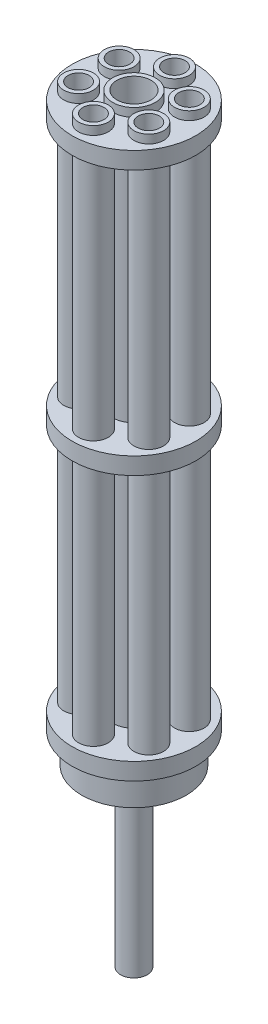
SolidWorks part; units mm, degrees
other "Markup1"
sketch "Sketch5" plane through (-15, 6, 15) normal (0, 1, 0) x (-1, 0, 0)
ref_plane "Front Plane" through (0, 0, 0) normal (0, 0, 1) x (1, 0, 0)
ref_plane "Top Plane" through (0, 0, 0) normal (0, 1, 0) x (1, 0, 0)
ref_plane "Right Plane" through (0, 0, 0) normal (1, 0, 0) x (0, 0, -1)
sketch "Sketch1" plane through (0, 0, 0) normal (0, 1, 0) x (1, 0, 0)
  circle A15 centre (0, 0) radius 14.5
  dimension "D1" = 29
extrude "Boss-Extrude1" add sketch "Sketch1" along normal blind 4
sketch "Sketch2" plane through (0, 4, 0) normal (0, 1, 0) x (1, 0, 0)
  line L0 (0, 0) -> (0, 9.5) construction
  line L1 (0, 0) -> (-8.2272, 4.75) construction
  line L2 (0, 0) -> (-8.2272, -4.75) construction
  line L3 (0, 9.5) -> (-8.2272, 4.75) construction
  line L4 (0, 0) -> (-2.4588, 9.1763) construction
  line L6 (0, 0) -> (-7.25, 12.5574) construction
  circle A0 centre (0, 0) radius 5
  circle A1 centre (0, 9.5) radius 3.48
  circle A2 centre (8.2272, 4.75) radius 3.48
  circle A3 centre (8.2272, -4.75) radius 3.48
  circle A4 centre (0, -9.5) radius 3.48
  circle A5 centre (-8.2272, -4.75) radius 3.48
  circle A6 centre (-8.2272, 4.75) radius 3.48
  circle A7 centre (0, 0) radius 4
  circle A8 centre (-8.2272, 4.75) radius 2.48
  circle A9 centre (0, 9.5) radius 2.48
  circle A10 centre (8.2272, 4.75) radius 2.48
  circle A11 centre (8.2272, -4.75) radius 2.48
  circle A12 centre (0, -9.5) radius 2.48
  circle A13 centre (-8.2272, -4.75) radius 2.48
  circle A14 centre (0, 0) radius 9.5 construction
  circle A15 centre (0, 0) radius 14.5 construction
  arc A16 (-6.7175, 6.7175) -> (-2.4588, 9.1763) centre (0, 0) cw construction
  arc A17 (6.7175, 6.7175) -> (9.1763, 2.4588) centre (0, 0) cw construction
  arc A18 (6.7175, 6.7175) -> (9.1763, 2.4588) centre (0, 0) cw construction
  point P17 (0, 0)
  point P31 (-6.0795, 5.99)
  point P32 (-2.1477, 8.26)
  point P33 (-2.4588, 9.1763)
  point P34 (-6.7175, 6.7175)
  dimension "D1" = 10
  dimension "D2" = 15
  dimension "D7" = 1
  dimension "D3" = 9.5
  dimension "D5" = 30
  dimension "D6" = 6
extrude "Boss-Extrude2" add sketch "Sketch2" along normal blind 2 and the other way blind 125
pattern_linear "LPattern4" count 3 spacing 62 along (0, -1, 0) of "Boss-Extrude1"
sketch "Sketch3" plane through (0, 4, 0) normal (0, 1, 0) x (1, 0, 0)
  circle A0 centre (0, 9.5) radius 2.48 construction
  circle A1 centre (0, 0) radius 4
  circle A2 centre (0, 0) radius 4
  circle A3 centre (-8.2272, 4.75) radius 2.48 construction
  circle A4 centre (-8.2272, -4.75) radius 2.48 construction
  circle A5 centre (0, -9.5) radius 2.48 construction
  circle A6 centre (8.2272, -4.75) radius 2.48 construction
  circle A7 centre (8.2272, 4.75) radius 2.48 construction
  circle A8 centre (0, 9.5) radius 2.48
  circle A9 centre (-8.2272, 4.75) radius 2.48
  circle A10 centre (-8.2272, -4.75) radius 2.48
  circle A11 centre (0, -9.5) radius 2.48
  circle A12 centre (8.2272, -4.75) radius 2.48
  circle A13 centre (8.2272, 4.75) radius 2.48
  dimension "D1" = 0
extrude "Cut-Extrude1" [suppressed] cut sketch "Sketch3" against normal through all
sketch "Sketch4" plane through (0, -124, 0) normal (0, -1, 0) x (1, 0, 0)
  circle A0 centre (0, 0) radius 5.2
  dimension "D1" = 10.4
extrude "Cut-Extrude2" [suppressed] cut sketch "Sketch4" against normal offset from surface (58 mm away) 4 up to face at (-8.2272, 4, -1.27)
sketch "Sketch6" plane through (0, -124, 0) normal (0, -1, 0) x (1, 0, 0)
  line L0 (-16.7447, 7) -> (-12.6984, 7) construction
  line L1 (-16.7447, 7) -> (-16.7447, 3) construction
  line L2 (-16.7447, 3) -> (-16.7447, 0) construction
  line L3 (-16.7447, 0) -> (-19.7447, 0) construction
  line L4 (-19.7447, 0) -> (0, 0) construction
  line L5 (0, 0) -> (0, 14.5) construction
  arc A0 (-13.874, 4.2145) -> (-16.7447, 3) centre (-16.7447, 7) cw
  arc A2 (-16.7447, 3) -> (-16.7447, -3) centre (-16.7447, 0) ccw
  arc A3 (-13.874, -4.2145) -> (-16.7447, -3) centre (-16.7447, -7) ccw
  arc A4 (-13.874, 4.2145) -> (-13.874, -4.2145) centre (0, 0) ccw
  circle A5 centre (-16.7447, 0) radius 1.75
  circle A6 centre (0, 0) radius 14.5 construction
  point P21 (-19.7447, 0)
  dimension "D1" = 90
  dimension "D3" = 3
  dimension "D4" = 4
  dimension "D6" = 3.5
  dimension "D2" = 90
  dimension "D5" = 8.4291
extrude "Boss-Extrude3" [suppressed] add sketch "Sketch6" against normal up to surface (4 mm away)
mirror "Mirror1" [suppressed] about plane through (0, 0, 0) normal (1, 0, 0)
sketch "Sketch7" plane through (0, 0, 0) normal (1, 0, 0) x (0, 0, -1)
  line L0 (-1.27, 6) -> (-8.23, 6) construction
  line L1 (-14.5, 6) -> (14.5, 6)
  line L2 (-14.5, 6) -> (-14.5, -124)
  line L3 (-14.5, -124) -> (14.5, -124)
  line L4 (14.5, 6) -> (14.5, -124)
  line L6 (-14.5, -124) -> (14.5, -124) construction
  point P11 (0, 6)
  dimension "D1" = 29
extrude "Short Cut" [suppressed] cut sketch "Sketch7" against normal through all and the other way through all
sketch "Sketch8" plane through (0, 4, 0) normal (0, 1, 0) x (1, 0, 0)
  circle A0 centre (-8.2272, -4.75) radius 2.48 construction
  circle A1 centre (0, -9.5) radius 2.48 construction
  circle A2 centre (8.2272, -4.75) radius 2.48 construction
  circle A3 centre (8.2272, 4.75) radius 2.48 construction
  circle A4 centre (0, 9.5) radius 2.48 construction
  circle A5 centre (-8.2272, 4.75) radius 2.48 construction
  circle A6 centre (-8.2272, -4.75) radius 2.48
  circle A7 centre (0, -9.5) radius 2.48
  circle A8 centre (8.2272, -4.75) radius 2.48
  circle A9 centre (8.2272, 4.75) radius 2.48
  circle A10 centre (0, 9.5) radius 2.48
  circle A11 centre (-8.2272, 4.75) radius 2.48
extrude "Cut-Extrude4" cut sketch "Sketch8" against normal up to surface (128 mm away) up to face at (0, -124, 14.5)
sketch "Sketch12" plane through (0, -124, 0) normal (0, -1, 0) x (1, 0, 0)
  circle A0 centre (0, 0) radius 3.125
  dimension "D1" = 6.25
extrude "Boss-Extrude4" add sketch "Sketch12" along normal blind 48
sketch "Sketch9" plane through (0, -172, 0) normal (0, -1, 0) x (1, 0, 0)
  line L0 (1.55, 1.49) -> (1.55, -1.49)
  line L1 (-2.15, 2.2678) -> (-2.15, -2.2678) construction
  arc A0 (1.55, 1.49) -> (1.55, -1.49) centre (0, 0) ccw
  circle A1 centre (0, 0) radius 3.125 construction
  dimension "D1" = 4.3
  dimension "D2" = 3.7
extrude "Cut-Extrude5" cut sketch "Sketch9" against normal up to surface (48 mm away) up to face at (0, -124, 3.125)
sketch "Sketch14" plane through (0, 4, 0) normal (0, 1, 0) x (1, 0, 0)
  circle A1 centre (0, 0) radius 4
  circle A2 centre (0, 0) radius 4
  dimension "D1" = 0
extrude "Cut-Extrude6" cut sketch "Sketch14" against normal up to surface (124 mm away) up to face at (-8.2272, -120, 8.23)
sketch "Sketch10" plane through (0, 0, 0) normal (1, 0, 0) x (0, 0, -1)
  line L0 (-14.5, 4) -> (-14.5, 0) construction
  line L1 (-14.5, 6) -> (14.5, 6)
  line L2 (-14.5, 6) -> (-14.5, -123)
  line L3 (-14.5, -123) -> (14.5, -123)
  line L4 (14.5, 6) -> (14.5, -123)
  line L5 (14.5, 0) -> (14.5, 4) construction
  line L6 (8.23, 6) -> (1.27, 6) construction
  line L7 (14.5, -123) -> (14.5, -124) construction
  dimension "D1" = 129
extrude "Short cut 2" [suppressed] cut sketch "Sketch10" against normal through all and the other way through all
sketch "Sketch16" plane through (0, -124, 0) normal (0, -1, 0) x (1, 0, 0)
  circle A0 centre (0, 9.5) radius 2.48 construction
  circle A1 centre (8.2272, 4.75) radius 2.48 construction
  circle A2 centre (8.2272, -4.75) radius 2.48 construction
  circle A3 centre (0, -9.5) radius 2.48 construction
  circle A4 centre (-8.2272, -4.75) radius 2.48 construction
  circle A5 centre (-8.2272, 4.75) radius 2.48 construction
  circle A6 centre (0, 9.5) radius 2.48
  circle A7 centre (8.2272, 4.75) radius 2.48
  circle A8 centre (8.2272, -4.75) radius 2.48
  circle A9 centre (0, -9.5) radius 2.48
  circle A10 centre (-8.2272, -4.75) radius 2.48
  circle A11 centre (-8.2272, 4.75) radius 2.48
  circle A12 centre (0, 0) radius 12.25
  dimension "D1" = 24.5
extrude "Boss-Extrude5" add sketch "Sketch16" along normal blind 7
sketch "Sketch15" plane through (0, 0, 0) normal (1, 0, 0) x (0, 0, -1)
  line L1 (-12.25, -135) -> (12.25, -135)
  line L2 (-12.25, -135) -> (-12.25, -172)
  line L3 (-12.25, -172) -> (12.25, -172)
  line L4 (12.25, -135) -> (12.25, -172)
  line L5 (-14.5, -124) -> (14.5, -124) construction
  line L6 (12.25, -131) -> (12.25, -124) construction
  line L7 (-12.25, -124) -> (-12.25, -131) construction
  line L8 (-3.125, -172) -> (3.125, -172) construction
  dimension "D1" = 11
extrude "Short Cut " [suppressed] cut sketch "Sketch15" against normal through all both and the other way through all contours L1 L4 L3 L2
sketch "Sketch17" plane through (0, 0, 0) normal (0, 0, 1) x (1, 0, 0)
  line L0 (14.5, -124) -> (14.5, -120) construction
  line L1 (-14.5, -120) -> (14.5, -120)
  line L2 (-14.5, -120) -> (-14.5, -128)
  line L3 (-14.5, -128) -> (14.5, -128)
  line L4 (14.5, -120) -> (14.5, -128)
  dimension "D1" = 8
extrude "Short Cut 3" [suppressed] cut sketch "Sketch17" against normal through all both and the other way through all
